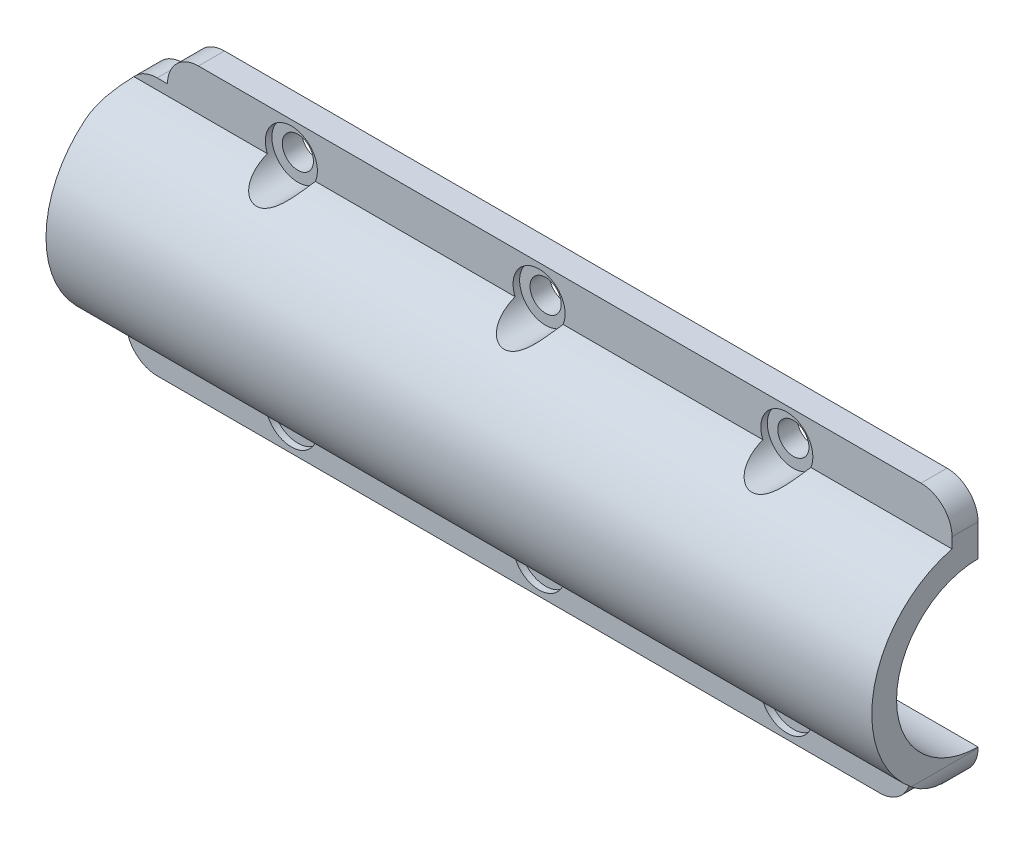
SolidWorks part; units mm, degrees
material "ABS"
ref_plane "X-Y Datum" through (0, 0, 0) normal (0, 0, 1) x (1, 0, 0)
ref_plane "X-Z Datum" through (0, 0, 0) normal (0, 1, 0) x (1, 0, 0)
ref_plane "Y-Z Datum" through (0, 0, 0) normal (1, 0, 0) x (0, 0, -1)
sketch "Sketch1" plane through (0, 0, 0) normal (1, 0, 0) x (0, 0, -1)
  line L0 (0, 22.225) -> (0, 17.4625) construction
  line L1 (-4, 22.225) -> (-4, 15.8396)
  line L2 (0, -22.225) -> (-4, -22.225)
  line L3 (-4, 11.8711) -> (-4, 11.3422)
  line L4 (-4, -15.8396) -> (-4, -22.225)
  line L5 (0, 12.5269) -> (0, 12.0269)
  line L6 (0, -12.5269) -> (0, -12.0269)
  line L15 (16.3195, -17.4625) -> (16.3195, 17.4625)
  line L17 (0, -12.5269) -> (0, -17.4625)
  line L18 (0, 17.4625) -> (0, 12.5269)
  line L27 (10.3195, 22.225) -> (0, 22.225) construction
  line L28 (10.3195, 22.225) -> (-4, 22.225)
  line L29 (0, 22.225) -> (0, 17.4625)
  line L32 (0, -22.225) -> (16.3195, -22.225)
  line L33 (16.3195, 17.4625) -> (0, 17.4625)
  line L36 (0, -17.4625) -> (0, -22.225)
  line L43 (0, -17.4625) -> (16.3195, -17.4625)
  arc A1 (0, -12.5269) -> (0, 12.5269) centre (0, 0) cw
  arc A2 (0, -12.5269) -> (0, 12.5269) centre (0, 0) ccw
  circle A3 centre (0, 0) radius 12.0269
  circle A4 centre (0, 0) radius 12.0269
  circle A5 centre (0, 0) radius 16.3369
  dimension "D5" = 4
  dimension "D2" = 0
extrude "Boss-Extrude1" add sketch "Sketch1" along normal blind 114.3 contours A5 L18 L1 | L18 A5 L17 | A5 L4 L17 region at (0, 19.1968, 2.0273) region at (0, 15.8496, 1.9703) region at (0, -19.1968, 2.0273)
sketch "Sketch2" plane through (0, 0, 4) normal (0, 0, 1) x (1, 0, 0)
  circle A0 centre (19.05, -17.376) radius 4
  circle A1 centre (57.15, -17.376) radius 4
  circle A2 centre (95.25, -17.376) radius 4
  point P0 (19.05, -17.376)
  point P1 (57.15, -17.376)
  point P3 (95.25, -17.376)
  dimension "D1" = 8
extrude "Cut-Extrude1" cut sketch "Sketch2" against normal blind 1 and the other way blind 6.35
hole_wizard "M4 Clearance Hole1" positions "Sketch7" profile "Sketch6" hole size "M4" standard "ANSI Metric" end condition through all
sketch "Sketch7" plane through (0, 0, 4) normal (0, 0, 1) x (1, 0, 0)
  point P0 (19.05, -17.376)
  point P3 (57.15, -17.376)
  point P6 (95.25, -17.376)
sketch "Sketch6" plane through (19.05, -17.376, 4) normal (1, 0, 0) x (0, -1, 0)
  line L0 (0, 0) -> (0, 4)
  line L1 (0, 4) -> (2.4, 4)
  line L2 (2.4, 4) -> (2.4, 0)
  line L5 (2.4, 0) -> (0, 0)
  line L11 (0, -6.35) -> (0, 107.95) construction
  dimension "Thru Hole Dia." = 4.8
  dimension "Thru Hole Depth" = 4
mirror "Mirror1" about plane through (0, 0, 0) normal (0, 1, 0) of "M4 Clearance Hole1", "Cut-Extrude1"
fillet "Fillet1" radius 4.7625 2 edges at (114.3, -22.225, 2) (0, 22.225, 2)
sketch "Sketch8" plane through (0, 0, 0) normal (-1, 0, 0) x (0, 0, 1)
  line L6 (4, 15.8396) -> (4, 17.4625)
  line L7 (4, 17.4625) -> (0, 17.4625)
  line L8 (0, 17.4625) -> (0, 12.5269)
  line L9 (0, -12.5269) -> (0, -22.225)
  line L10 (0, -22.225) -> (4, -22.225)
  line L11 (4, -22.225) -> (4, -15.8396)
  line L12 (4, 15.8396) -> (4, 17.4625)
  line L13 (4, 17.4625) -> (0, 17.4625)
  line L15 (0, -12.5269) -> (0, -22.225)
  line L16 (0, -22.225) -> (4, -22.225)
  line L17 (4, -22.225) -> (4, -15.8396)
  line L18 (0, 17.4625) -> (0, 12.5269)
  arc A2 (0, -12.5269) -> (0, 12.5269) centre (0, 0) ccw
  arc A3 (4, -15.8396) -> (4, 15.8396) centre (0, 0) ccw
  arc A5 (4, -15.8396) -> (4, 15.8396) centre (0, 0) ccw
  arc A6 (0, -12.5269) -> (0, 12.5269) centre (0, 0) ccw
  dimension "D1" = 0
extrude "Boss-Extrude2" add sketch "Sketch8" along normal blind 6.35 contours L12 L13 L18 A6 L15 L16 L17 A5
sketch "Sketch9" plane through (114.3, 0, 0) normal (1, 0, 0) x (0, 0, -1)
  line L6 (-4, -15.8396) -> (-4, -17.4625)
  line L7 (-4, -17.4625) -> (0, -17.4625)
  line L8 (0, -17.4625) -> (0, -12.5269)
  line L9 (0, 12.5269) -> (0, 22.225)
  line L10 (0, 22.225) -> (-4, 22.225)
  line L11 (-4, 22.225) -> (-4, 15.8396)
  line L12 (-4, -15.8396) -> (-4, -17.4625)
  line L13 (-4, -17.4625) -> (0, -17.4625)
  line L14 (0, -17.4625) -> (0, -12.5269)
  line L16 (0, 22.225) -> (-4, 22.225)
  line L17 (-4, 22.225) -> (-4, 15.8396)
  line L18 (0, 12.5269) -> (0, 22.225)
  arc A2 (0, 12.5269) -> (0, -12.5269) centre (0, 0) ccw
  arc A3 (-4, 15.8396) -> (-4, -15.8396) centre (0, 0) ccw
  arc A5 (-4, 15.8396) -> (-4, -15.8396) centre (0, 0) ccw
  arc A6 (0, 12.5269) -> (0, -12.5269) centre (0, 0) ccw
  dimension "D1" = 0
extrude "Boss-Extrude3" add sketch "Sketch9" along normal blind 6.35
fillet "Fillet2" radius 4.7625 4 edges at (120.65, -17.4625, 2) (120.65, 22.225, 2) (-6.35, 17.4625, 2) (-6.35, -22.225, 2)
